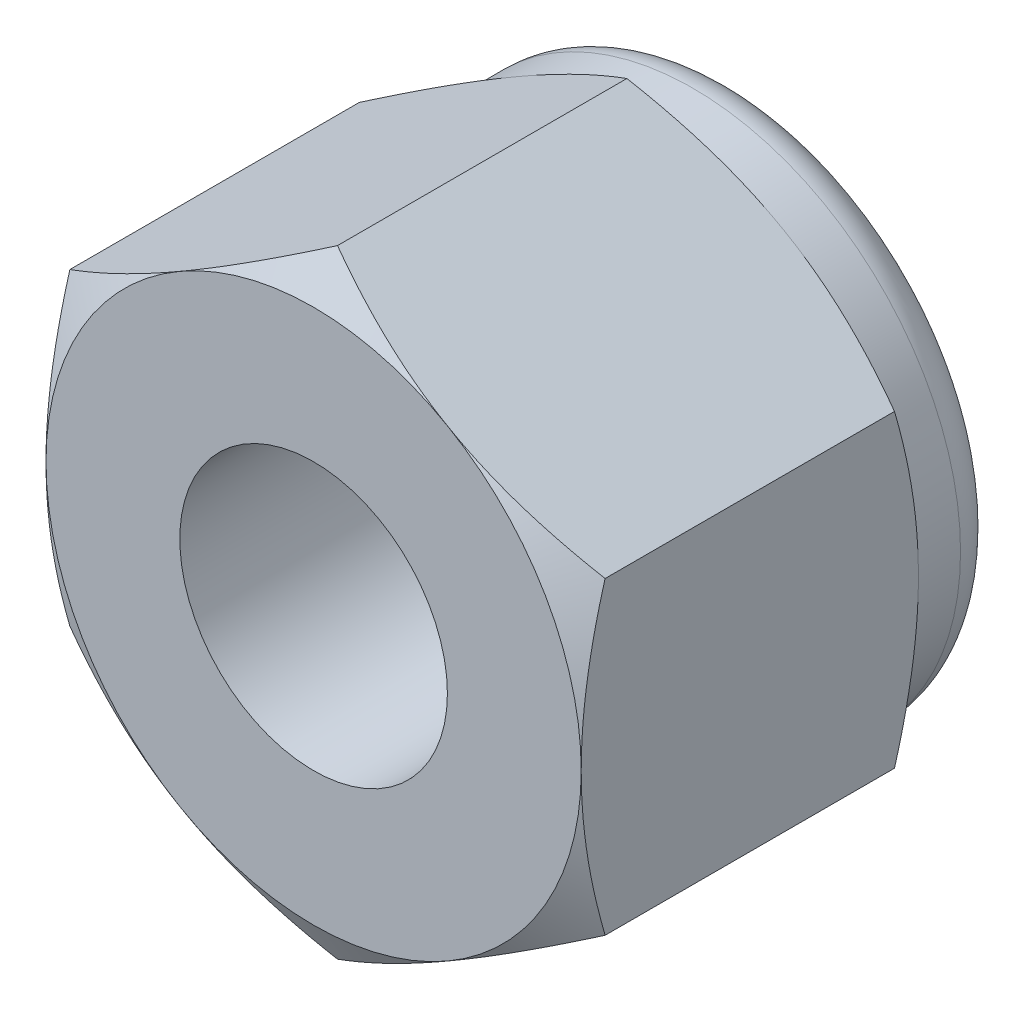
SolidWorks part; units mm, degrees
material "Acier allié"
ref_plane "Plan1" through (0, 0, 0) normal (0, 0, 1) x (1, 0, 0)
ref_plane "Plan2" through (0, 0, 0) normal (0, 1, 0) x (1, 0, 0)
ref_plane "Plan3" through (0, 0, 0) normal (1, 0, 0) x (0, 0, -1)
sketch "Esquisse1" plane through (0, 0, 0) normal (0, 0, 1) x (1, 0, 0)
  line L0 (0, 0) -> (4, 0) construction
  line L1 (4, -2.3094) -> (4, 2.3094)
  line L2 (0, 0) -> (4, 2.3094) construction
  line L3 (0, 0) -> (0, 4.6188) construction
  line L4 (4, 2.3094) -> (0, 4.6188)
  line L5 (4, -2.3094) -> (0, -4.6188)
  line L6 (-4, -2.3094) -> (0, -4.6188)
  line L7 (-4, -2.3094) -> (-4, 2.3094)
  line L8 (-4, 2.3094) -> (0, 4.6188)
  circle A0 centre (0, 0) radius 4 construction
  circle A1 centre (0, 0) radius 4.6188 construction
  dimension "a" = 8
  dimension "D1" = 30
extrude "Base-Extrusion" add sketch "Esquisse1" against normal blind 5.04
sketch "Esquisse2" plane through (0, 0, 0) normal (0, 1, 0) x (1, 0, 0)
  line L0 (-4, 0) -> (-9.3648, 0)
  line L1 (0, 5.04) -> (0, 0) construction
  line L2 (-4, 5.04) -> (-9.3648, 5.04)
  line L3 (-9.3648, 5.04) -> (-9.3648, 0)
  line L5 (-8.3648, 2.52) -> (-4, 5.04)
  line L6 (0, 5.04) -> (0, 0) construction
  line L7 (-4, 0) -> (-8.3648, 2.52)
  dimension "D1" = 30
  dimension "D2" = 1
  dimension "D3" = 30
revolve "Enlèvement de matière-Révolution1" cut sketch "Esquisse2" angle 360 about L6
sketch "Esquisse3" plane through (0, 0, 0) normal (0, 0, 1) x (1, 0, 0)
  circle A0 centre (0, 0) radius 2.5
  dimension "dn" = 5
extrude "Enlèv. mat.-Extru.1" cut sketch "Esquisse3" against normal through all
ref_axis "Axe1" through (0, 0, -50) along (0, 0, 1)
sketch "Esquisse4" plane through (0, 0, 0) normal (1, 0, 0) x (0, 0, -1)
  line L0 (5.04, 4) -> (5.67, 4)
  line L1 (5.04, 0) -> (5.04, 3.4641) construction
  line L2 (5.04, 4) -> (4.6827, 4.6188) construction
  line L3 (6.3, 4) -> (6.3, 2.3094) construction
  line L4 (5.775, 2.3094) -> (5.04, 2.3094)
  line L5 (5.04, 2.3094) -> (5.04, 4)
  line L7 (0, 3.4641) -> (0, 0) construction
  line L8 (0, 0) -> (5.04, 0) construction
  line L9 (6.3, 3.37) -> (6.3, 3.1547)
  line L10 (6.3, 3.1547) -> (5.775, 3.1547)
  line L11 (5.775, 3.1547) -> (5.775, 2.3094)
  line L12 (4.6827, 2.3094) -> (0.3573, 2.3094) construction
  arc A0 (6.3, 3.37) -> (5.67, 4) centre (5.67, 3.37) ccw
  dimension "D3" = 0.63
  dimension "h" = 6.3
  dimension "D2" = 1.05
revolve "Boss.-Révol.1" add sketch "Esquisse4" angle 360 about L8
sketch "Esquisse5" plane through (0, 0, 0) normal (0, 0, 1) x (1, 0, 0)
  circle A0 centre (0, 0) radius 2
  circle A1 centre (0, 0) radius 2.5 construction
  circle A2 centre (0, 0) radius 2.5
  dimension "D1" = 4
extrude "Boss.-Extru.1" add sketch "Esquisse5" against normal up to surface (5.04 mm away) up to face at (2.3094, 0, -5.04)
cosmetic thread "Représentation de filetage1" parameters "D2"=5
equation "\"D2@Esquisse4\"=\"h@Esquisse4\"/6"
equation "\"D3@Esquisse4\"=\"h@Esquisse4\"/10"
equation "\"h@Base-Extrusion\"=\"h@Esquisse4\"*0.8"
equation "\"D1@Esquisse5\"=\"dn@Esquisse3\"*0.8"
equation "\"D2@Représentation de filetage1\"=\"dn@Esquisse3\""
